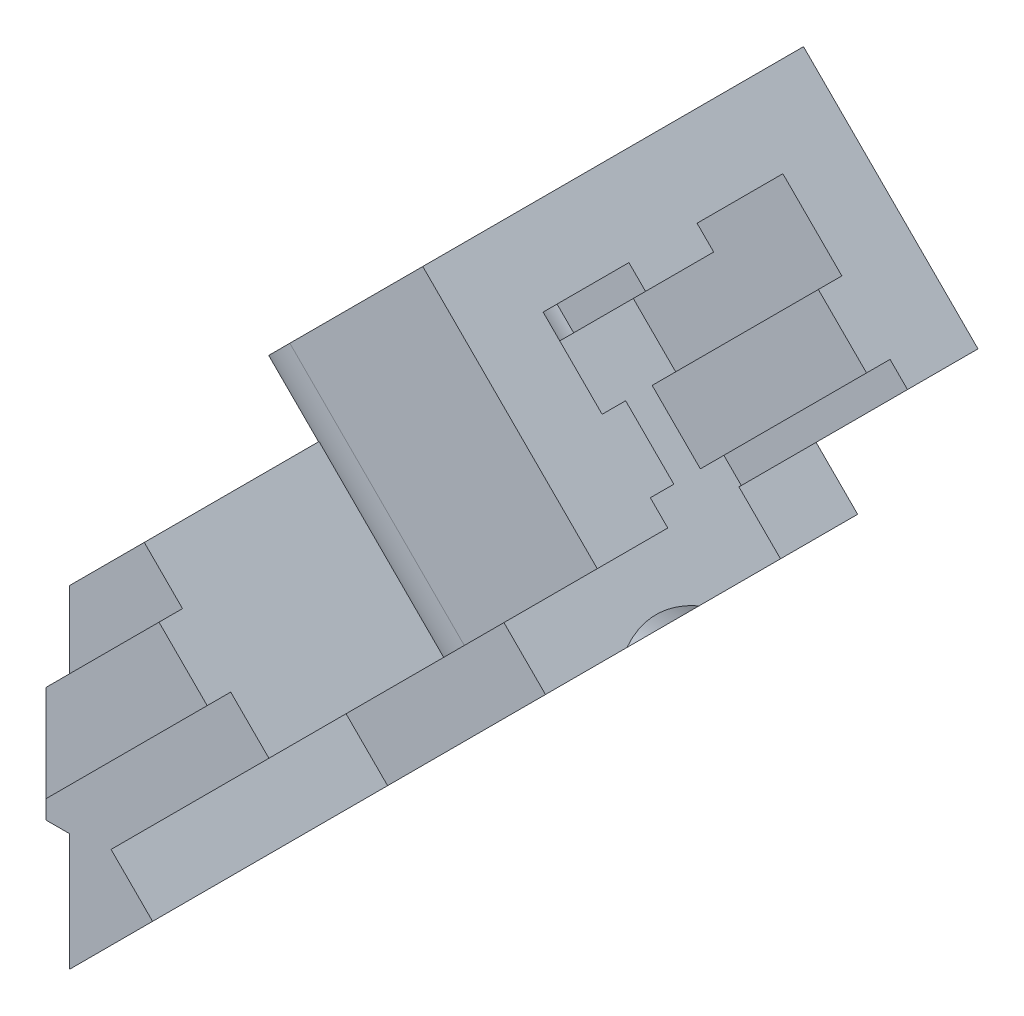
SolidWorks part; units mm, degrees
ref_plane "Front Plane" through (0, 0, 0) normal (0, 0, 1) x (1, 0, 0)
ref_plane "Top Plane" through (0, 0, 0) normal (0, 1, 0) x (1, 0, 0)
ref_plane "Right Plane" through (0, 0, 0) normal (1, 0, 0) x (0, 0, -1)
sketch "Esquisse1" plane through (0, 0, 0) normal (0, 0, 1) x (1, 0, 0)
  line L0 (0, 0) -> (0, 5)
  line L1 (0, 5) -> (-1, 5)
  line L2 (-1, 5) -> (-1, 7.9)
  line L3 (-1, 7.9) -> (0, 7.9)
  line L4 (0, 7.9) -> (0, 14.1421)
  line L5 (0, 14.1421) -> (3.182, 17.3241)
  line L6 (3.182, 17.3241) -> (10.253, 10.253)
  line L7 (10.253, 10.253) -> (0, 0)
  dimension "D1" = 2.9
  dimension "D2" = 45
  dimension "D3" = 10
  dimension "D4" = 5
  dimension "D5" = 1
  dimension "D6" = 14.5
extrude "Main Extrusion" add sketch "Esquisse1" along normal mid plane 30
sketch "Esquisse2" plane through (0, 0, 0) normal (0.7071, -0.7071, 0) x (0, 0, -1)
  line L0 (15, 0) -> (15, 14.5) construction
  line L1 (5, 5) -> (15, 5)
  line L2 (5, 5) -> (5, 14.5)
  line L3 (5, 14.5) -> (15, 14.5)
  line L4 (15, 5) -> (15, 14.5)
  line L5 (-15, 14.5) -> (15, 14.5) construction
  line L6 (-15, 0) -> (15, 0) construction
  dimension "D1" = 5
  dimension "D2" = 10
extrude "Window Extrusion" cut sketch "Esquisse2" against normal blind 2.5
sketch "Esquisse5" plane through (-1.7678, 1.7678, 0) normal (0.7071, -0.7071, 0) x (0, 0, -1)
  line L0 (15, 14.5) -> (5, 14.5) construction
  line L2 (5, 5) -> (15, 5) construction
  circle A0 centre (10, 11.5) radius 1.25
  point P4 (10, 14.5)
  dimension "D1" = 2.5
  dimension "D2" = 6.5
extrude "Window Hole Extrusion" cut sketch "Esquisse5" against normal through all
sketch "Esquisse7" plane through (10.253, 10.253, 0) normal (0.7071, 0.7071, 0) x (0, 0, -1)
  line L0 (-5.1, 2.5) -> (-5.1, 3.55)
  line L1 (-5.1, 3.55) -> (-4.1, 3.55)
  line L2 (-4.1, 3.55) -> (-4.1, 6.45)
  line L3 (-4.1, 6.45) -> (-5.1, 6.45)
  line L4 (-5.1, 6.45) -> (-5.1, 10)
  line L6 (-15, 10) -> (15, 10) construction
  line L7 (-15, 0) -> (-15, 10) construction
  line L18 (-8.1, 10) -> (-5.1, 10)
  line L19 (-8.1, 10) -> (-8.1, 2.5)
  line L20 (-8.1, 2.5) -> (-5.1, 2.5)
  dimension "D1" = 1
  dimension "D2" = 2.9
  dimension "D3" = 3
  dimension "D4" = 6.9
  dimension "D5" = 3.55
  dimension "D6" = 7.5
extrude "Fixation Top MakerBeam Extrusion" add sketch "Esquisse7" along normal blind 10
mirror "Window Symetry" about plane through (0, 0, 0) normal (0, 0, 1) of "Fixation Top MakerBeam Extrusion", "Window Extrusion", "Window Hole Extrusion"
sketch "Esquisse3" plane through (-1, 0, 0) normal (-1, 0, 0) x (0, 0, 1)
  line L0 (15, 7.9) -> (15, 5) construction
  line L1 (0, -55) -> (0, 55) construction
  circle A0 centre (0, 6.45) radius 1.5
  point P5 (15, 6.45)
  dimension "D1" = 3
extrude "Window Hole Fixation" cut sketch "Esquisse3" against normal through all
ref_plane "Plan1" through (3, 0, 0) normal (-1, 0, 0) x (0, 0, 1)
sketch "Esquisse4" plane through (3, 0, 0) normal (-1, 0, 0) x (0, 0, 1)
  circle A0 centre (0, 6.45) radius 4.1
  arc A1 (0.3841, 5) -> (0.3841, 7.9) centre (0, 6.45) ccw construction
  dimension "D1" = 8.2
extrude "Central Fixation" cut sketch "Esquisse4" against normal through all
sketch "Esquisse6" plane through (0, 0, 15) normal (0, 0, 1) x (1, 0, 0)
  line L0 (0, 10.8894) -> (4.8083, 15.6978)
  line L1 (8.4853, 12.0208) -> (3.182, 17.3241) construction
  line L2 (4.8083, 15.6978) -> (6.8589, 13.6472)
  line L3 (6.8589, 13.6472) -> (0, 6.7882)
  line L4 (0, 6.7882) -> (0, 10.8894)
  line L5 (0, 5) -> (0, 0) construction
  point P6 (5.8336, 14.6725)
  point P7 (5.8336, 14.6725)
  dimension "D1" = 2.9
extrude "Boss.-Extru.2" add sketch "Esquisse6" along normal blind 1
sketch "Esquisse8" plane through (17.3241, 17.3241, 0) normal (0.7071, 0.7071, 0) x (0, 0, -1)
  line L0 (-8.1, 10) -> (-1.45, 10)
  line L1 (-1.45, 10) -> (-1.45, 9)
  line L2 (-1.45, 9) -> (1.45, 9)
  line L3 (1.45, 9) -> (1.45, 10)
  line L4 (1.45, 10) -> (8.1, 10)
  line L5 (8.1, 10) -> (8.1, 13)
  line L6 (8.1, 13) -> (-8.1, 13)
  line L7 (-8.1, 13) -> (-8.1, 10)
  line L8 (0, 55) -> (0, -55) construction
  point P9 (0, 9)
  dimension "D1" = 3
  dimension "D2" = 2.9
  dimension "D3" = 1
extrude "Boss.-Extru.6" add sketch "Esquisse8" against normal blind 12
fillet "Congé1" radius 4 2 edges at (0.7071, 16.9706, -8.1) (0.7071, 16.9706, 8.1)
sketch "Esquisse11" plane through (-9.1924, 9.1924, 0) normal (-0.7071, 0.7071, 0) x (0, 0, 1)
  line L0 (-8.1, 24.5) -> (8.1, 24.5) construction
  circle A0 centre (0, 19.5) radius 1.6
  point P4 (0, 24.5)
  dimension "D1" = 3.2
  dimension "D2" = 5
extrude "Enlèv. mat.-Extru.2" cut sketch "Esquisse11" against normal through all
